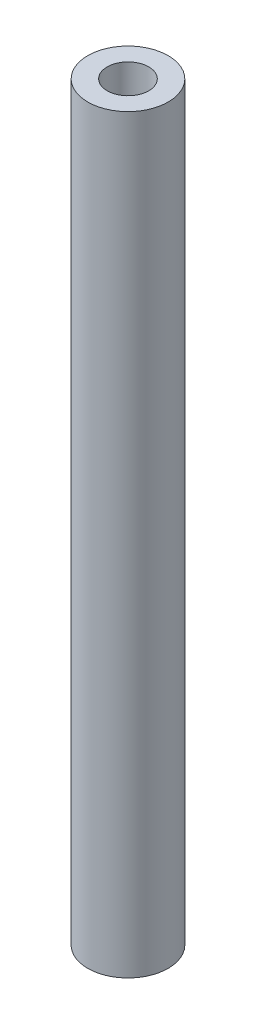
SolidWorks part; units mm, degrees
ref_plane "Front Plane" through (0, 0, 0) normal (0, 0, 1) x (1, 0, 0)
ref_plane "Top Plane" through (0, 0, 0) normal (0, 1, 0) x (1, 0, 0)
ref_plane "Right Plane" through (0, 0, 0) normal (1, 0, 0) x (0, 0, -1)
sketch "Sketch1" plane through (0, 0, 0) normal (0, 1, 0) x (1, 0, 0)
  circle A0 centre (0, 0) radius 1.55
  circle A1 centre (0, 0) radius 3
  dimension "D1" = 3.1
  dimension "D2" = 6
extrude "Boss-Extrude1" add sketch "Sketch1" along normal blind 56
